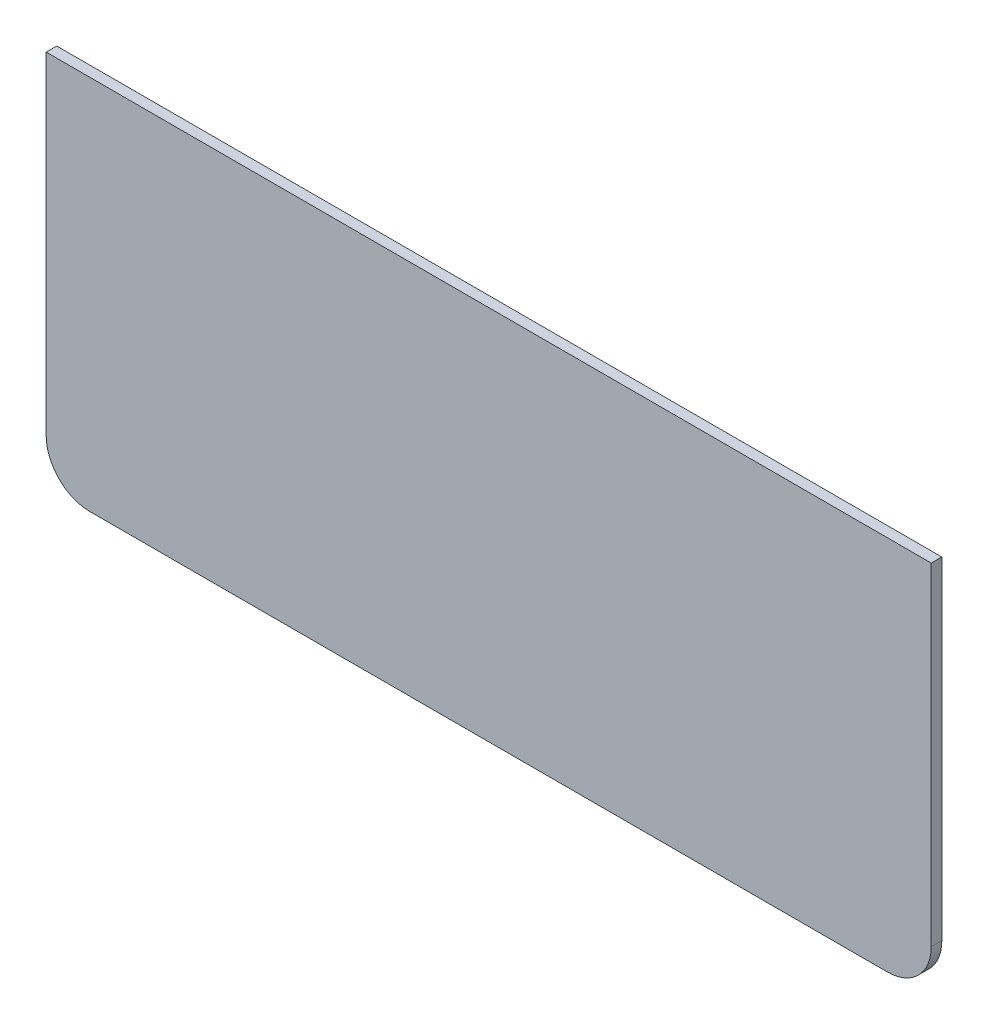
SolidWorks part; units mm, degrees
material "5052-H32"
ref_plane "Front Plane" through (0, 0, 0) normal (0, 0, 1) x (1, 0, 0)
ref_plane "Top Plane" through (0, 0, 0) normal (0, 1, 0) x (1, 0, 0)
ref_plane "Right Plane" through (0, 0, 0) normal (1, 0, 0) x (0, 0, -1)
sketch "Sketch2" plane through (0, 0, 0) normal (0, 0, 1) x (1, 0, 0)
  line L0 (-53.5866, 40.5355) -> (212.7634, 40.5355)
  line L1 (212.7634, 40.5355) -> (212.7634, -72.6395)
  line L2 (212.7634, -72.6395) -> (-53.5866, -72.6395)
  line L3 (-53.5866, -72.6395) -> (-53.5866, 40.5355)
  dimension "D1" = 113.175
  dimension "D2" = 266.35
extrude "Boss-Extrude1" add sketch "Sketch2" along normal blind 3.175
fillet "Fillet1" radius 13.175 2 edges at (-53.5866, -72.6395, 1.5875) (212.7634, -72.6395, 1.5875)
equation "\"L\"= 500"
equation "\"W\"= 260"
equation "\"H\"= 110"
equation "\"Compartment Width\"= 90"
equation "\"T\"= 4.7625 * 2 / 3"
equation "\"Inside Fillet Radius\"= 10"
equation "\"D1@Fillet1\"=\"Inside Fillet Radius\"+\"T\""
equation "\"D1@Sketch2\"=\"T\"+\"H\""
equation "\"D2@Sketch2\"=2*\"T\"+\"W\""
equation "\"D1@Boss-Extrude1\"=\"T\""
